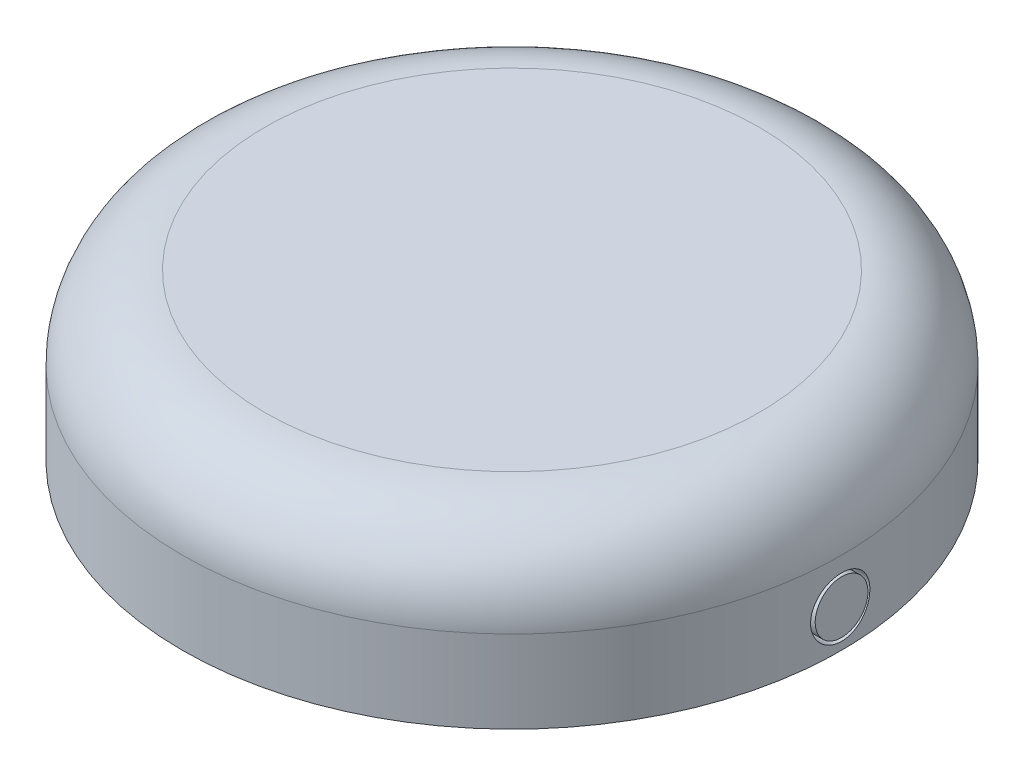
SolidWorks part; units mm, degrees
ref_plane "前视基准面" through (0, 0, 0) normal (0, 0, 1) x (1, 0, 0)
ref_plane "上视基准面" through (0, 0, 0) normal (0, 1, 0) x (1, 0, 0)
ref_plane "右视基准面" through (0, 0, 0) normal (1, 0, 0) x (0, 0, -1)
sketch "草图1" plane through (0, 0, 0) normal (0, 1, 0) x (1, 0, 0)
  circle A0 centre (0, 0) radius 100
  dimension "D1" = 200
extrude "凸台-拉伸1" add sketch "草图1" along normal blind 50
fillet "圆角1" radius 25 1 edges at (0, 50, 100)
shell "抽壳1" thickness 10 removed face at (0, 0, 100)
sketch "草图7" plane through (0, 0, 0) normal (1, 0, 0) x (0, 0, -1)
  circle A0 centre (0, 11.3803) radius 9
  dimension "D1" = 18
extrude "切除-拉伸1" cut sketch "草图7" against normal blind 100 and the other way blind 100
ref_plane "基准面5" through (90, 0, 0) normal (1, 0, 0) x (0, 0, -1)
sketch "草图8" plane through (90, 0, 0) normal (1, 0, 0) x (0, 0, -1)
  circle A0 centre (0, 11.3803) radius 8
  dimension "D1" = 16
extrude "凸台-拉伸2" add sketch "草图8" along normal blind 10 separate body
sketch "草图9" plane through (90, 0, 0) normal (1, 0, 0) x (0, 0, -1)
  line L1 (-9.8181, 31.3803) -> (9.8181, 31.3803)
  line L2 (-9.8181, 31.3803) -> (-9.8181, 1.3803)
  line L3 (-9.8181, 1.3803) -> (9.8181, 1.3803)
  line L4 (9.8181, 31.3803) -> (9.8181, 1.3803)
  line L5 (-9.8181, 31.3803) -> (9.8181, 1.3803) construction
  line L6 (-9.8181, 1.3803) -> (9.8181, 31.3803) construction
  point P0 (0, 16.3803)
  dimension "D1" = 30
extrude "凸台-拉伸3" add sketch "草图9" against normal blind 3
ref_plane "基准面6" through (-90, 0, 0) normal (1, 0, 0) x (0, 0, -1)
sketch "草图10" plane through (-90, 0, 0) normal (1, 0, 0) x (0, 0, -1)
  circle A0 centre (0, 11.3803) radius 8
extrude "凸台-拉伸4" add sketch "草图10" against normal blind 10 separate body
sketch "草图11" plane through (-90, 0, 0) normal (1, 0, 0) x (0, 0, -1)
  line L1 (-9.8181, 26.8803) -> (9.8181, 26.8803)
  line L2 (-9.8181, 26.8803) -> (-9.8181, 1.8803)
  line L3 (-9.8181, 1.8803) -> (9.8181, 1.8803)
  line L4 (9.8181, 26.8803) -> (9.8181, 1.8803)
  line L5 (-9.8181, 26.8803) -> (9.8181, 1.8803) construction
  line L6 (-9.8181, 1.8803) -> (9.8181, 26.8803) construction
  point P0 (0, 14.3803)
  dimension "D1" = 25
extrude "凸台-拉伸5" add sketch "草图11" along normal blind 3
